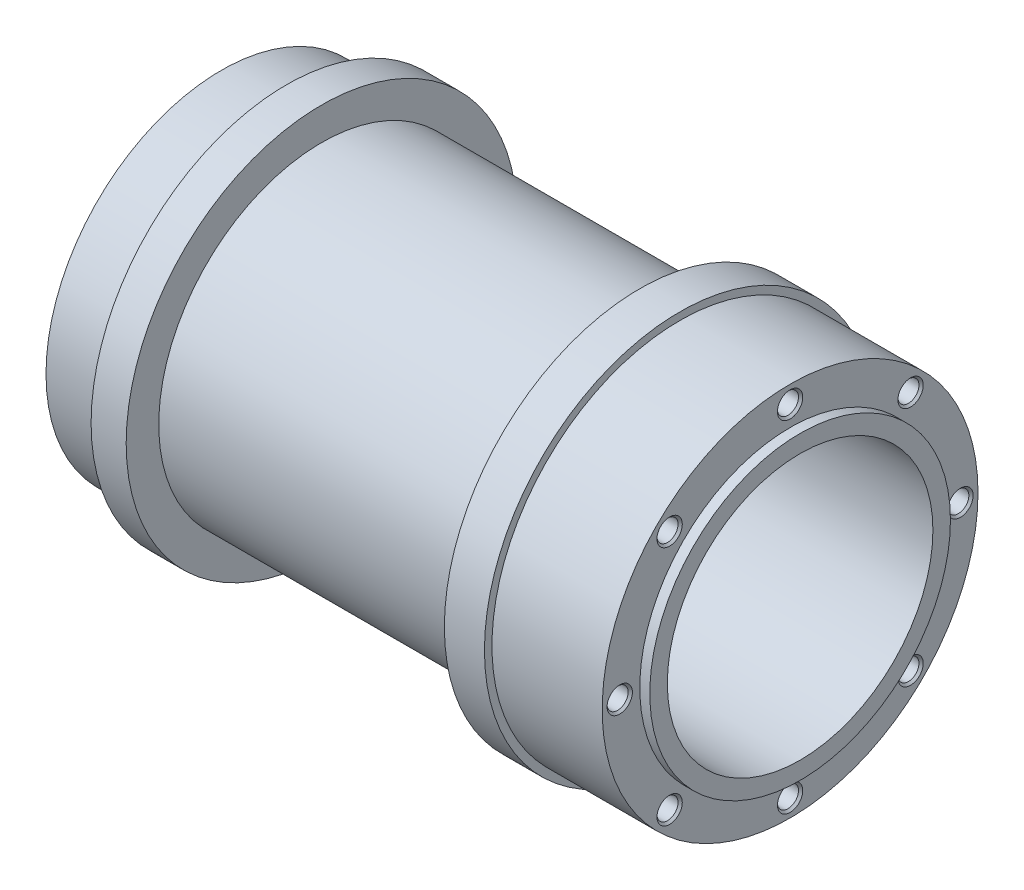
SolidWorks part; units mm, degrees
material "Stop 1060"
ref_plane "Płaszczyzna przednia" through (0, 0, 0) normal (0, 0, 1) x (1, 0, 0)
ref_plane "Płaszczyzna górna" through (0, 0, 0) normal (0, 1, 0) x (1, 0, 0)
ref_plane "Płaszczyzna prawa" through (0, 0, 0) normal (1, 0, 0) x (0, 0, -1)
sketch "Szkic1" plane through (0, 0, 0) normal (0, 0, 1) x (1, 0, 0)
  line L0 (-115.5, 16) -> (-115.5, 35)
  line L1 (-111.5, 16) -> (-115.5, 16)
  line L2 (-111.5, 16) -> (-111.5, 26.5)
  line L3 (-102.5, 35) -> (-115.5, 35)
  line L4 (-102.5, 39) -> (-102.5, 35)
  line L5 (-24, 37.5) -> (-2, 37.5)
  line L6 (-24, 39) -> (-24, 37.5)
  line L7 (-2, 37.5) -> (-2, 30)
  line L8 (-111.5, 26.5) -> (0, 26.5)
  line L9 (-24, 39) -> (-32, 39)
  line L10 (-95.5, 32.5) -> (-32, 32.5)
  line L11 (-95.5, 39) -> (-95.5, 32.5)
  line L12 (-95.5, 39) -> (-102.5, 39)
  line L13 (-32, 32.5) -> (-32, 39)
  line L14 (0, 30) -> (0, 26.5)
  line L15 (-2, 30) -> (0, 30)
  line L16 (0, 0) -> (-129.2658, 0) construction
revolve "Obrót1" add sketch "Szkic1" angle 360 about L16
hole_wizard "Otwór gwintowany M51" positions "Szkic2" profile "Szkic4" tap size "M5" standard "DIN"
sketch "Szkic2" plane through (-2, 0, 0) normal (1, 0, 0) x (0, 0, -1)
  point P0 (34, 0)
  point P15 (0, 0)
  point P39 (24.0416, -24.0416)
  point P40 (0, -34)
  point P41 (-24.0416, -24.0416)
  point P42 (-34, 0)
  point P43 (-24.0416, 24.0416)
  point P44 (0, 34)
  point P45 (24.0416, 24.0416)
  point P46 (0, 0)
  dimension "D1" = 34
  dimension "D2" = 8
sketch "Szkic4" plane through (-2, 0, -34) normal (0, 1, 0) x (0, 0, -1)
  line L0 (0, 0) -> (0, 17.2618)
  line L1 (0, 17.2618) -> (2.1, 16)
  line L2 (2.1, 16) -> (2.1, 0.425)
  line L3 (2.1, 0.425) -> (2.525, 0)
  line L5 (2.525, 0) -> (0, 0)
  line L6 (-2.1, 0.425) -> (-2.525, 0) construction
  line L10 (0, 17.2618) -> (-2.1, 16) construction
  line L11 (0, -6.35) -> (0, 107.95) construction
  dimension "Średnica wiertła gwintu" = 4.2
  dimension "Głębokość otworu gwintowanego" = 16
  dimension "Średnica zewnętrznego pogłębienia stożkowego" = 5.05
  dimension "Kąt zewnętrznego pogłębienia stożkowego" = 90
  dimension "Kąt wiertła" = 118
cosmetic thread "Gwint otworu1"
cosmetic thread "Gwint otworu2"
cosmetic thread "Gwint otworu3"
cosmetic thread "Gwint otworu4"
cosmetic thread "Gwint otworu5"
cosmetic thread "Gwint otworu6"
cosmetic thread "Gwint otworu7"
cosmetic thread "Gwint otworu8"
